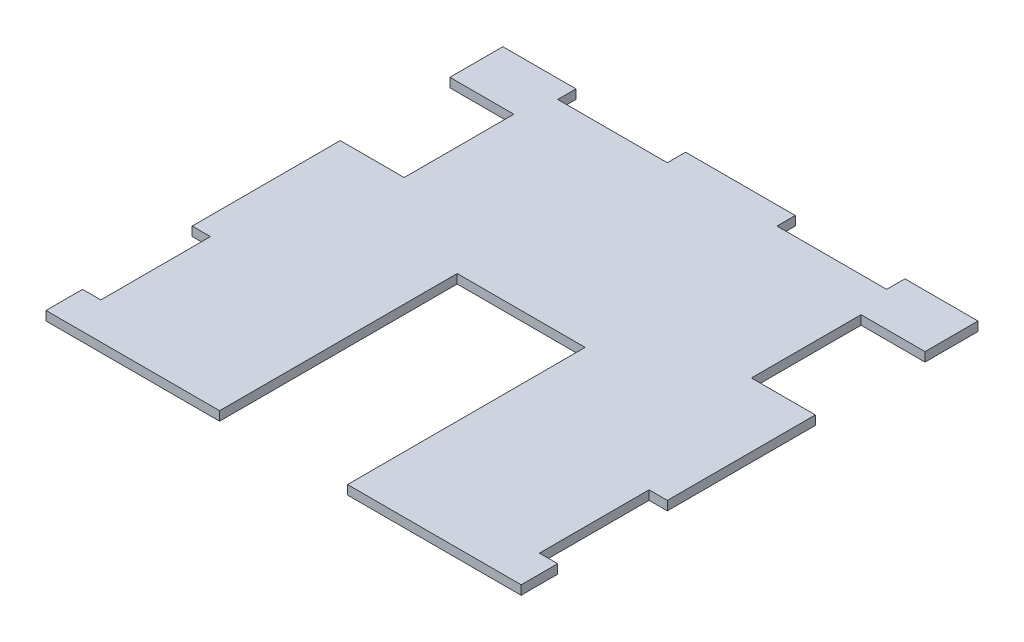
SolidWorks part; units mm, degrees
ref_plane "Front Plane" through (0, 0, 0) normal (0, 0, 1) x (1, 0, 0)
ref_plane "Top Plane" through (0, 0, 0) normal (0, 1, 0) x (1, 0, 0)
ref_plane "Right Plane" through (0, 0, 0) normal (1, 0, 0) x (0, 0, -1)
sketch "Sketch1" plane through (0, 0, 0) normal (0, 1, 0) x (1, 0, 0)
  line L0 (0, -55) -> (0, 55) construction
  line L1 (-165.1, -76.2) -> (165.1, -76.2)
  line L2 (-165.1, -76.2) -> (-165.1, 76.2)
  line L3 (-165.1, 76.2) -> (165.1, 76.2)
  line L4 (165.1, -76.2) -> (165.1, 76.2)
  line L5 (-165.1, -76.2) -> (165.1, 76.2) construction
  line L6 (-165.1, 76.2) -> (165.1, -76.2) construction
  line L7 (-165.1, -76.2) -> (-31.75, -76.2)
  line L8 (-165.1, -76.2) -> (-165.1, -241.3)
  line L9 (-165.1, -241.3) -> (-31.75, -241.3)
  line L10 (-31.75, -76.2) -> (-31.75, -241.3)
  line L11 (31.75, -76.2) -> (31.75, -241.3)
  line L12 (165.1, -241.3) -> (31.75, -241.3)
  line L13 (165.1, -76.2) -> (165.1, -241.3)
  line L14 (165.1, -76.2) -> (31.75, -76.2)
  line L15 (-44.45, -76.2) -> (-44.45, -241.3)
  line L16 (44.45, -76.2) -> (44.45, -241.3)
  point P0 (0, 0)
  dimension "D1" = 330.2
  dimension "D2" = 152.4
  dimension "D3" = 317.5
  dimension "D4" = 63.5
  dimension "D5" = 12.7
extrude "Boss-Extrude1" add sketch "Sketch1" along normal blind 6.35 contours L15 L1 L8 L9 | L14 L16 L12 L13 | L1 L7 L14 L4 L3 L2 region at (0, 0, 0) region at (-104.775, 0, 158.75) region at (104.775, 0, 158.75)
sketch "Sketch2" plane through (0, 6.35, 0) normal (0, 1, 0) x (1, 0, 0)
  line L0 (165.1, -241.3) -> (165.1, 76.2) construction
  line L1 (165.1, 39.37) -> (120.65, 39.37)
  line L2 (165.1, 39.37) -> (165.1, -36.83)
  line L3 (165.1, -36.83) -> (120.65, -36.83)
  line L4 (120.65, 39.37) -> (120.65, -36.83)
  line L5 (-165.1, 76.2) -> (165.1, 76.2) construction
  line L6 (165.1, -139.7) -> (152.4, -139.7)
  line L7 (165.1, -139.7) -> (165.1, -215.9)
  line L8 (165.1, -215.9) -> (152.4, -215.9)
  line L9 (152.4, -139.7) -> (152.4, -215.9)
  line L10 (0, -55) -> (0, 55) construction
  line L11 (-165.1, -215.9) -> (-152.4, -215.9)
  line L12 (-152.4, -139.7) -> (-152.4, -215.9)
  line L13 (-165.1, -139.7) -> (-152.4, -139.7)
  line L14 (-165.1, -139.7) -> (-165.1, -215.9)
  line L15 (-165.1, -36.83) -> (-120.65, -36.83)
  line L16 (-120.65, 39.37) -> (-120.65, -36.83)
  line L17 (-165.1, 39.37) -> (-120.65, 39.37)
  line L18 (-165.1, 39.37) -> (-165.1, -36.83)
  line L19 (-114.3, 63.5) -> (-38.1, 63.5)
  line L20 (114.3, 76.2) -> (38.1, 76.2)
  line L21 (114.3, 76.2) -> (114.3, 63.5)
  line L22 (114.3, 63.5) -> (38.1, 63.5)
  line L23 (38.1, 76.2) -> (38.1, 63.5)
  line L24 (-38.1, 76.2) -> (-38.1, 63.5)
  line L25 (-114.3, 76.2) -> (-38.1, 76.2)
  line L26 (-114.3, 76.2) -> (-114.3, 63.5)
  dimension "D1" = 44.45
  dimension "D2" = 12.7
  dimension "D3" = 76.2
  dimension "D4" = 76.2
  dimension "D5" = 36.83
  dimension "D6" = 215.9
  dimension "D7" = 76.2
  dimension "D8" = 12.7
  dimension "D9" = 76.2
extrude "Cut-Extrude1" cut sketch "Sketch2" against normal through all
sketch "Sketch3" plane through (0, 6.35, 0) normal (0, 1, 0) x (1, 0, 0)
  line L0 (-44.45, -76.2) -> (44.45, -76.2) construction
  line L1 (-44.45, -25.4) -> (-31.75, -25.4)
  line L2 (-44.45, -25.4) -> (-44.45, 25.4)
  line L3 (-44.45, 25.4) -> (-31.75, 25.4)
  line L4 (-31.75, -25.4) -> (-31.75, 25.4)
  line L5 (0, -55) -> (0, 55) construction
  line L6 (44.45, 25.4) -> (31.75, 25.4)
  line L7 (31.75, -25.4) -> (31.75, 25.4)
  line L8 (44.45, -25.4) -> (31.75, -25.4)
  line L9 (44.45, -25.4) -> (44.45, 25.4)
  dimension "D1" = 50.8
  dimension "D2" = 12.7
  dimension "D3" = 50.8
